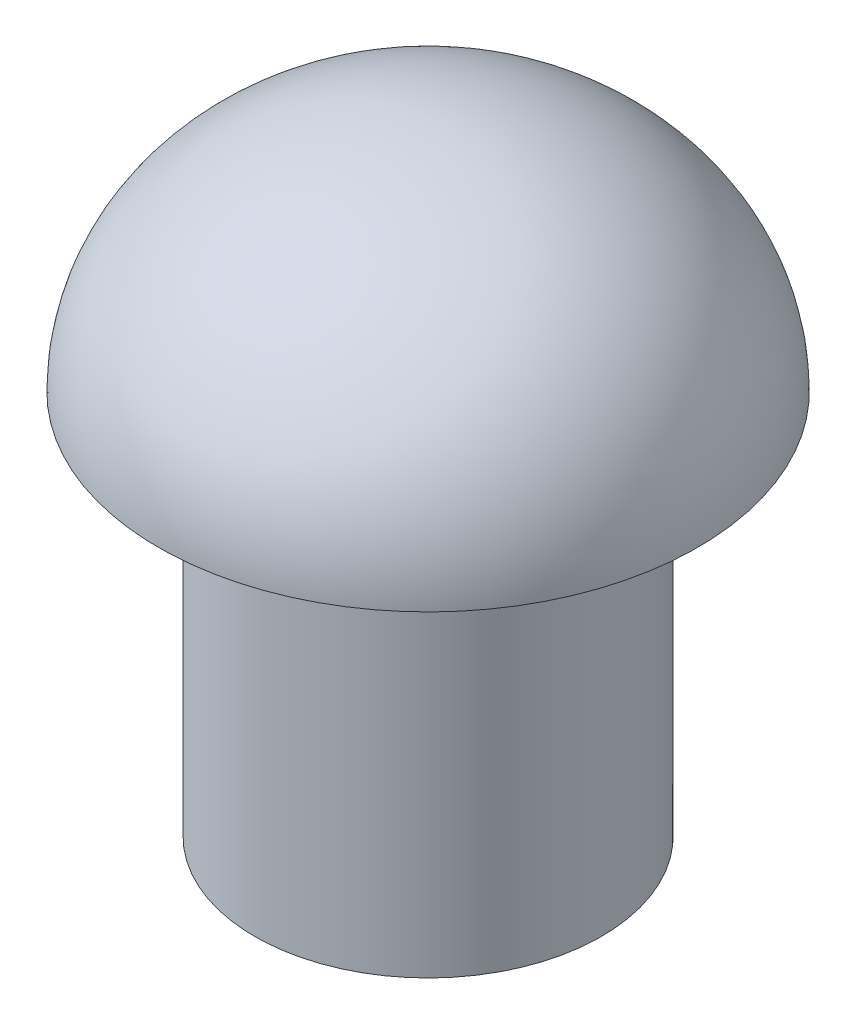
SolidWorks part; units mm, degrees
ref_plane "Front Plane" through (0, 0, 0) normal (0, 0, 1) x (1, 0, 0)
ref_plane "Top Plane" through (0, 0, 0) normal (0, 1, 0) x (1, 0, 0)
ref_plane "Right Plane" through (0, 0, 0) normal (1, 0, 0) x (0, 0, -1)
sketch "Sketch1" plane through (0, 0, 0) normal (1, 0, 0) x (0, 0, -1)
  line L1 (0, 0) -> (3.5, 0)
  line L2 (0, 0) -> (0, 3)
  ellipse E0 centre (0, 0) end of major axis (-3.5, 0) minor radius 3 (3.5, 0) -> (0, 3) ccw
  dimension "D1" = 3.5
  dimension "D2" = 3
ref_axis "Axis1" through (0, 0, 0) along (0, 1, 0)
revolve "Revolve5" add sketch "Sketch1" angle 360 about axis through (0, 0, 0) along (0, 1, 0) region at (0, 1.2732, -1.4854)
sketch "Sketch3" plane through (0, 0, 0) normal (0, -1, 0) x (1, 0, 0)
  line L1 (-1.591, -1.591) -> (1.591, -1.591) construction
  line L2 (-1.591, -1.591) -> (-1.591, 1.591) construction
  line L3 (-1.591, 1.591) -> (1.591, 1.591) construction
  line L4 (1.591, -1.591) -> (1.591, 1.591) construction
  line L5 (-1.591, -1.591) -> (1.591, 1.591) construction
  line L6 (-1.591, 1.591) -> (1.591, -1.591) construction
  circle A0 centre (0, 0) radius 2.25
  point P0 (0, 0)
  dimension "D1" = 4.5
extrude "Boss-Extrude1" add sketch "Sketch3" along normal blind 5
sketch "Sketch4" plane through (0, -5, 0) normal (0, -1, 0) x (1, 0, 0)
  line L1 (-1.5, -1.5) -> (1.5, -1.5)
  line L2 (-1.5, -1.5) -> (-1.5, 1.5)
  line L3 (-1.5, 1.5) -> (1.5, 1.5)
  line L4 (1.5, -1.5) -> (1.5, 1.5)
  line L5 (-1.5, -1.5) -> (1.5, 1.5) construction
  line L6 (-1.5, 1.5) -> (1.5, -1.5) construction
  point P0 (0, 0)
  dimension "D1" = 3
extrude "Cut-Extrude1" cut sketch "Sketch4" against normal blind 2
